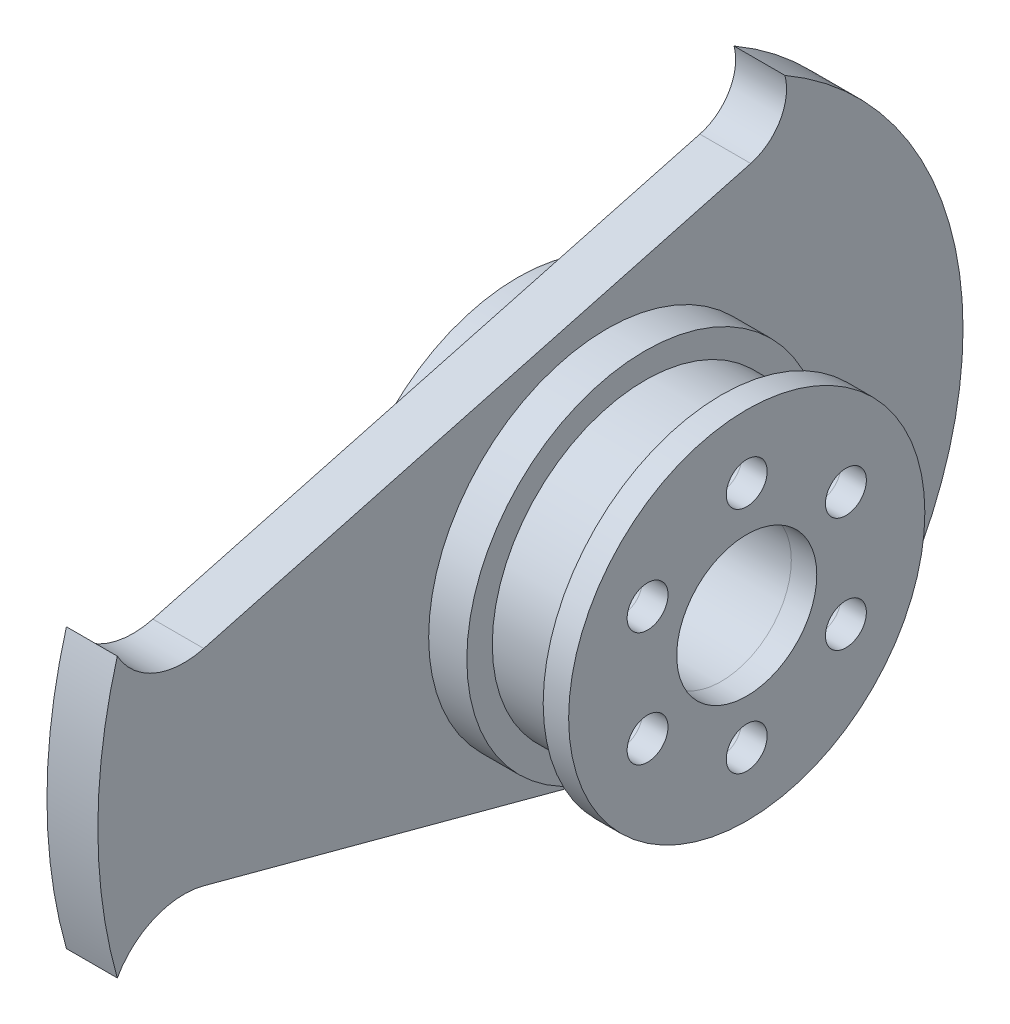
SolidWorks part; units mm, degrees
material "Alum Plate"
ref_plane "Front Plane" through (0, 0, 0) normal (0, 0, 1) x (1, 0, 0)
ref_plane "Top Plane" through (0, 0, 0) normal (0, 1, 0) x (1, 0, 0)
ref_plane "Right Plane" through (0, 0, 0) normal (1, 0, 0) x (0, 0, -1)
other "Center of Mass"
sketch "Sketch3" plane through (0, 0, 0) normal (1, 0, 0) x (0, 0, -1)
  circle A1 centre (0, 0) radius 63.5
  dimension "D1" = 127
extrude "Boss-Extrude1" add sketch "Sketch3" along normal mid plane 6.35
sketch "Sketch4" plane through (3.175, 0, 0) normal (1, 0, 0) x (0, 0, -1)
  line L0 (0, 0) -> (0, 14.2875) construction
  line L1 (-4.7625, 0) -> (-4.7625, 14.2875)
  line L2 (4.7625, 0) -> (4.7625, 14.2875)
  arc A0 (-4.7625, 0) -> (4.7625, 0) centre (0, 0) ccw
  arc A1 (4.7625, 14.2875) -> (-4.7625, 14.2875) centre (0, 14.2875) ccw
  point P3 (0, 7.1438)
  point P8 (0, 19.05)
  dimension "D1" = 4.7625
  dimension "D2" = 19.05
extrude "Cut-Extrude1" cut sketch "Sketch4" against normal through all
pattern_circular "CirPattern1" count 6 over 360 about axis through (3.175, 0, 0) along (1, 0, 0) of "Cut-Extrude1"
fillet "Fillet1" radius 2.54 6 edges at (0, 0, 9.525) (0, -8.2489, 4.7625) (0, -8.2489, -4.7625) (0, 0, -9.525) (0, 8.2489, 4.7625) (0, 8.2489, -4.7625)
sketch "Sketch5" plane through (3.175, 0, 0) normal (1, 0, 0) x (0, 0, -1)
  line L12 (-8.5725, 10.4486) -> (-9.9921, 11.2682)
  line L14 (-8.5725, 10.4486) -> (-9.9921, 11.2682)
  line L16 (-4.7625, 14.2875) -> (-4.7625, 12.6483)
  line L18 (-4.7625, 14.2875) -> (-4.7625, 12.6483)
  line L20 (4.7625, 12.6483) -> (4.7625, 14.2875)
  line L22 (4.7625, 12.6483) -> (4.7625, 14.2875)
  line L36 (9.9921, 11.2682) -> (8.5725, 10.4486)
  line L38 (9.9921, 11.2682) -> (8.5725, 10.4486)
  line L40 (13.335, 2.1997) -> (14.7546, 3.0193)
  line L42 (13.335, 2.1997) -> (14.7546, 3.0193)
  line L44 (14.7546, -3.0193) -> (13.335, -2.1997)
  line L46 (14.7546, -3.0193) -> (13.335, -2.1997)
  line L48 (8.5725, -10.4486) -> (9.9921, -11.2682)
  line L49 (8.5725, -10.4486) -> (9.9921, -11.2682)
  line L50 (4.7625, -14.2875) -> (4.7625, -12.6483)
  line L51 (4.7625, -14.2875) -> (4.7625, -12.6483)
  line L52 (-4.7625, -12.6483) -> (-4.7625, -14.2875)
  line L53 (-4.7625, -12.6483) -> (-4.7625, -14.2875)
  line L54 (-9.9921, -11.2682) -> (-8.5725, -10.4486)
  line L55 (-9.9921, -11.2682) -> (-8.5725, -10.4486)
  line L56 (-13.335, -2.1997) -> (-14.7546, -3.0193)
  line L57 (-13.335, -2.1997) -> (-14.7546, -3.0193)
  line L58 (-14.7546, 3.0193) -> (-13.335, 2.1997)
  line L59 (-14.7546, 3.0193) -> (-13.335, 2.1997)
  arc A6 (4.7625, 14.2875) -> (-4.7625, 14.2875) centre (0, 14.2875) ccw
  arc A7 (14.7546, 3.0193) -> (9.9921, 11.2682) centre (12.3733, 7.1438) ccw
  arc A8 (9.9921, -11.2682) -> (14.7546, -3.0193) centre (12.3733, -7.1437) ccw
  arc A9 (-4.7625, -14.2875) -> (4.7625, -14.2875) centre (0, -14.2875) ccw
  arc A10 (-14.7546, -3.0193) -> (-9.9921, -11.2682) centre (-12.3733, -7.1438) ccw
  arc A11 (-9.9921, 11.2682) -> (-14.7546, 3.0193) centre (-12.3733, 7.1437) ccw
  arc A12 (4.7625, 14.2875) -> (-4.7625, 14.2875) centre (0, 14.2875) ccw
  arc A13 (14.7546, 3.0193) -> (9.9921, 11.2682) centre (12.3733, 7.1438) ccw
  arc A14 (9.9921, -11.2682) -> (14.7546, -3.0193) centre (12.3733, -7.1437) ccw
  arc A15 (-4.7625, -14.2875) -> (4.7625, -14.2875) centre (0, -14.2875) ccw
  arc A16 (-14.7546, -3.0193) -> (-9.9921, -11.2682) centre (-12.3733, -7.1438) ccw
  arc A17 (-9.9921, 11.2682) -> (-14.7546, 3.0193) centre (-12.3733, 7.1437) ccw
  arc A24 (-13.335, -2.1997) -> (-13.335, 2.1997) centre (-14.605, 0) ccw
  arc A28 (-13.335, -2.1997) -> (-13.335, 2.1997) centre (-14.605, 0) ccw
  arc A32 (-8.5725, 10.4486) -> (-4.7625, 12.6483) centre (-7.3025, 12.6483) ccw
  arc A36 (-8.5725, 10.4486) -> (-4.7625, 12.6483) centre (-7.3025, 12.6483) ccw
  arc A38 (4.7625, 12.6483) -> (8.5725, 10.4486) centre (7.3025, 12.6483) ccw
  arc A40 (4.7625, 12.6483) -> (8.5725, 10.4486) centre (7.3025, 12.6483) ccw
  arc A42 (13.335, 2.1997) -> (13.335, -2.1997) centre (14.605, 0) ccw
  arc A43 (13.335, 2.1997) -> (13.335, -2.1997) centre (14.605, 0) ccw
  arc A44 (8.5725, -10.4486) -> (4.7625, -12.6483) centre (7.3025, -12.6483) ccw
  arc A45 (8.5725, -10.4486) -> (4.7625, -12.6483) centre (7.3025, -12.6483) ccw
  arc A46 (-4.7625, -12.6483) -> (-8.5725, -10.4486) centre (-7.3025, -12.6483) ccw
  arc A47 (-4.7625, -12.6483) -> (-8.5725, -10.4486) centre (-7.3025, -12.6483) ccw
  dimension "D1" = 0
extrude "Boss-Extrude2" add sketch "Sketch5" against normal up to surface (6.35 mm away) separate body up to face at (-3.175, 0, 0)
sketch "Sketch6" plane through (-3.175, 0, 0) normal (-1, 0, 0) x (0, 0, 1)
  line L0 (0, -22.225) -> (0, -19.05) construction
  circle A0 centre (0, 0) radius 22.225
  arc A1 (-4.7625, -14.2875) -> (4.7625, -14.2875) centre (0, -14.2875) ccw construction
  dimension "D1" = 3.175
extrude "Boss-Extrude3" add sketch "Sketch6" along normal blind 4.7625 separate body
mirror "Mirror1" about plane through (0, 0, 0) normal (1, 0, 0) of bodies 105
sketch "Sketch7" plane through (7.9375, 0, 0) normal (1, 0, 0) x (0, 0, -1)
  circle A0 centre (0, 0) radius 19.05
  arc A1 (-9.9921, 11.2682) -> (-14.7546, 3.0193) centre (-12.3733, 7.1437) ccw construction
extrude "Boss-Extrude4" add sketch "Sketch7" along normal blind 9.525 separate body
sketch "Sketch9" plane through (17.4625, 0, 0) normal (1, 0, 0) x (0, 0, -1)
  circle A0 centre (0, 0) radius 22.225 construction
  circle A1 centre (0, 0) radius 22.225
extrude "Boss-Extrude6" add sketch "Sketch9" along normal blind 3.175
sketch "Sketch10" plane through (20.6375, 0, 0) normal (1, 0, 0) x (0, 0, -1)
  line L0 (0, 0) -> (0, 14.2875) construction
  circle A0 centre (0, 0) radius 8.7376
  circle A1 centre (0, 14.2875) radius 2.5527
  arc A2 (4.7625, 14.2875) -> (-4.7625, 14.2875) centre (0, 14.2875) ccw construction
  circle A3 centre (12.3733, 7.1438) radius 2.5527
  circle A4 centre (12.3733, -7.1437) radius 2.5527
  circle A5 centre (0, -14.2875) radius 2.5527
  circle A6 centre (-12.3733, -7.1438) radius 2.5527
  circle A7 centre (-12.3733, 7.1437) radius 2.5527
  point P20 (0, 0)
  dimension "D1" = 17.4752
  dimension "D2" = 5.1054
  dimension "D3" = 6
extrude "Cut-Extrude2" cut sketch "Sketch10" against normal through all
sketch "Sketch11" plane through (3.175, 0, 0) normal (1, 0, 0) x (0, 0, -1)
  line L0 (-50.2852, 12.8221) -> (17.9605, 31.1085)
  line L1 (-63.5, 0) -> (63.5, 0) construction
  line L2 (44.45, 0) -> (63.5, 0)
  line L3 (0, 0) -> (-61.0726, 17.3893) construction
  line L4 (-61.0726, 17.3893) -> (-51.3912, 0) construction
  line L5 (0, 0) -> (22.225, 38.4948) construction
  line L6 (22.225, 38.4948) -> (32.5397, 0) construction
  arc A0 (-61.0726, 17.3893) -> (-50.2852, 12.8221) centre (-52.7505, 22.0226) ccw
  circle A1 centre (0, 0) radius 63.5 construction
  arc A2 (17.9605, 31.1085) -> (22.225, 38.4948) centre (16.3996, 36.9339) ccw
  arc A3 (22.225, 38.4948) -> (44.45, 0) centre (0, 0) cw
  arc A4 (63.5, 0) -> (-61.0726, 17.3893) centre (0, 0) ccw
  dimension "D1" = 9.525
  dimension "D3" = 44.45
  dimension "D5" = 25.4
  dimension "D6" = 15
  dimension "D2" = 45
  dimension "D4" = 45
extrude "Cut-Extrude3" cut sketch "Sketch11" against normal through all
mirror "Mirror2" about plane through (0, 0, 0) normal (0, 1, 0) of "Cut-Extrude3"
